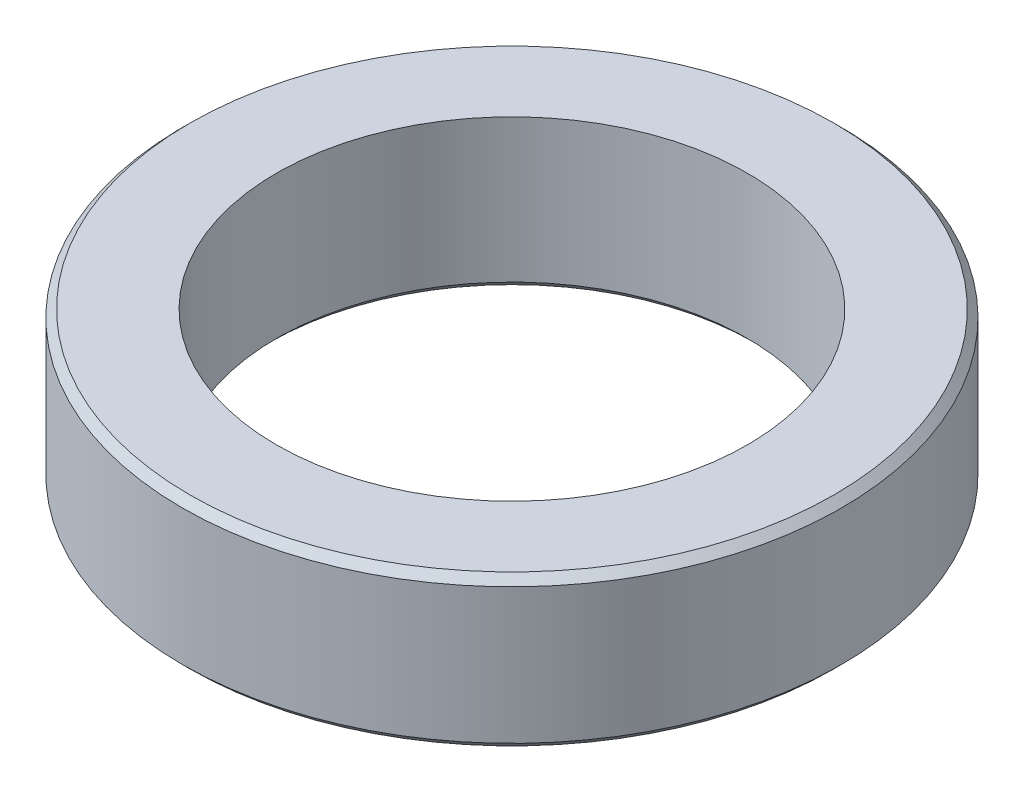
SolidWorks part; units mm, degrees
ref_plane "Front Plane" through (0, 0, 0) normal (0, 0, 1) x (1, 0, 0)
ref_plane "Top Plane" through (0, 0, 0) normal (0, 1, 0) x (1, 0, 0)
ref_plane "Right Plane" through (0, 0, 0) normal (1, 0, 0) x (0, 0, -1)
sketch "Sketch1" plane through (0, 0, 0) normal (0, 1, 0) x (1, 0, 0)
  circle A0 centre (0, 0) radius 79.375
  circle A1 centre (0, 0) radius 111.125
  dimension "D1" = 158.75
  dimension "D2" = 31.75
extrude "Boss-Extrude1" add sketch "Sketch1" along normal blind 50.8
chamfer "Chamfer1" distance 2.54 angle 45 3 edges at (0, 50.8, 111.125) (0, 0, 111.125) (0, 0, 79.375)
equation "\"shoulder offset\"= 1.25"
equation "\"ID\"=6.17"
equation "\"L\"= 2"
equation "\"D1@Sketch1\"=\"ID\"+\"ID offset\""
equation "\"D2@Sketch1\"=\"shoulder offset\""
equation "\"D1@Boss-Extrude1\"=\"L\""
equation "\"ID offset\"= .08"
